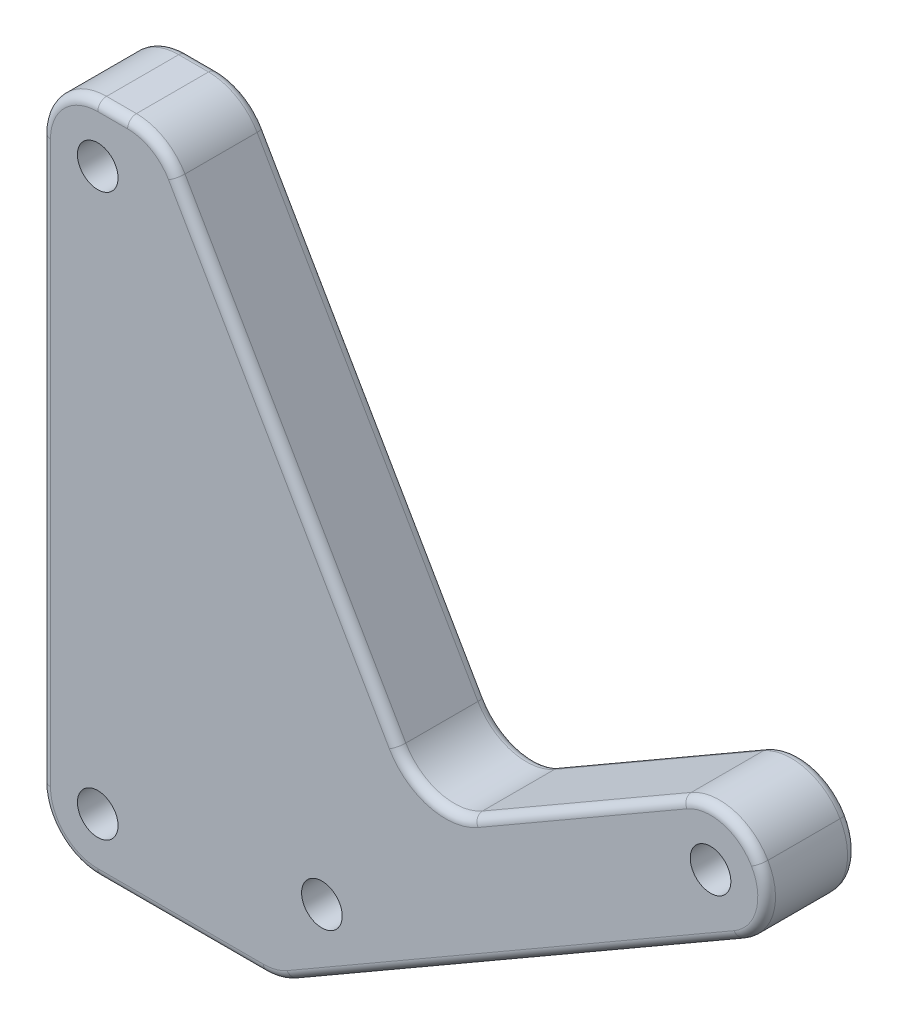
SolidWorks part; units mm, degrees
ref_plane "Front Plane" through (0, 0, 0) normal (0, 0, 1) x (1, 0, 0)
ref_plane "Top Plane" through (0, 0, 0) normal (0, 1, 0) x (1, 0, 0)
ref_plane "Right Plane" through (0, 0, 0) normal (1, 0, 0) x (0, 0, -1)
sketch "Sketch1" plane through (0, 0, 0) normal (0, 0, 1) x (1, 0, 0)
  line L0 (0, 235.9818) -> (-30, 287.9434)
  line L1 (0, 235.9818) -> (34.641, 255.9818)
  line L2 (-1.6589, 235.9818) -> (22.689, 235.9818) construction
  line L3 (-30, 287.9434) -> (-43.3989, 287.9434)
  line L4 (-43.3989, 287.9434) -> (-43.3989, 211.7434)
  line L5 (-43.3989, 211.7434) -> (-16.5823, 211.7434)
  line L6 (-16.5823, 211.7434) -> (40.991, 244.9833)
  line L7 (40.991, 244.9833) -> (34.641, 255.9818)
  line L10 (37.816, 250.4826) -> (-29.2823, 211.7434) construction
  circle A0 centre (-37.0489, 218.0934) radius 2.3
  circle A1 centre (-37.0489, 281.5934) radius 2.3
  circle A2 centre (32.3168, 247.3076) radius 2.3
  circle A3 centre (-11.6773, 221.9076) radius 2.3
  point P20 (0, 0)
  point P21 (0, 0)
  point P22 (0, 0)
  point P23 (-12.748, 221.2894)
  dimension "D11" = 4.6
  dimension "D6" = 4.6
  dimension "D1" = 30
  dimension "D2" = 12.7
  dimension "D3" = 40
  dimension "D4" = 50.8
  dimension "D5" = 76.2
  dimension "D7" = 60
  dimension "D8" = 6.35
  dimension "D9" = 6.35
  dimension "D10" = 6.35
  dimension "D12" = 6.35
extrude "Boss-Extrude1" add sketch "Sketch1" along normal blind 10.16
fillet "Fillet1" radius 6.35 7 edges at (-30, 287.9434, 5.08) (-16.5823, 211.7434, 5.08) (-43.3989, 211.7434, 5.08) (-43.3989, 287.9434, 5.08) (34.641, 255.9818, 5.08) (40.991, 244.9833, 5.08) (0, 235.9818, 5.08)
fillet "Fillet3" radius 1 26 edges at (17.3205, 245.9818, 10.16) (17.3205, 245.9818, 0) (-15.671, 263.1247, 0) (-30.4912, 287.0926, 0) (-35.3575, 287.9434, 0) (-41.539, 286.0835, 0) (-43.3989, 249.8434, 0) (-41.539, 213.6032, 0) (-27.6663, 211.7434, 0) (-16.6402, 211.9597, 0) (10.1915, 227.2012, 0) (10.1915, 227.2012, 10.16) (-16.6402, 211.9597, 10.16) (-27.6663, 211.7434, 10.16) (-41.539, 213.6032, 10.16) (-43.3989, 249.8434, 10.16) (-41.539, 286.0835, 10.16) (-35.3575, 287.9434, 10.16) (-30.4912, 287.0926, 10.16) (-15.671, 263.1247, 10.16) (33.9603, 253.4412, 10.16) (38.4504, 245.6641, 10.16) (0.6808, 238.5225, 10.16) (0.6808, 238.5225, 0) (33.9603, 253.4412, 0) (38.4504, 245.6641, 0)
